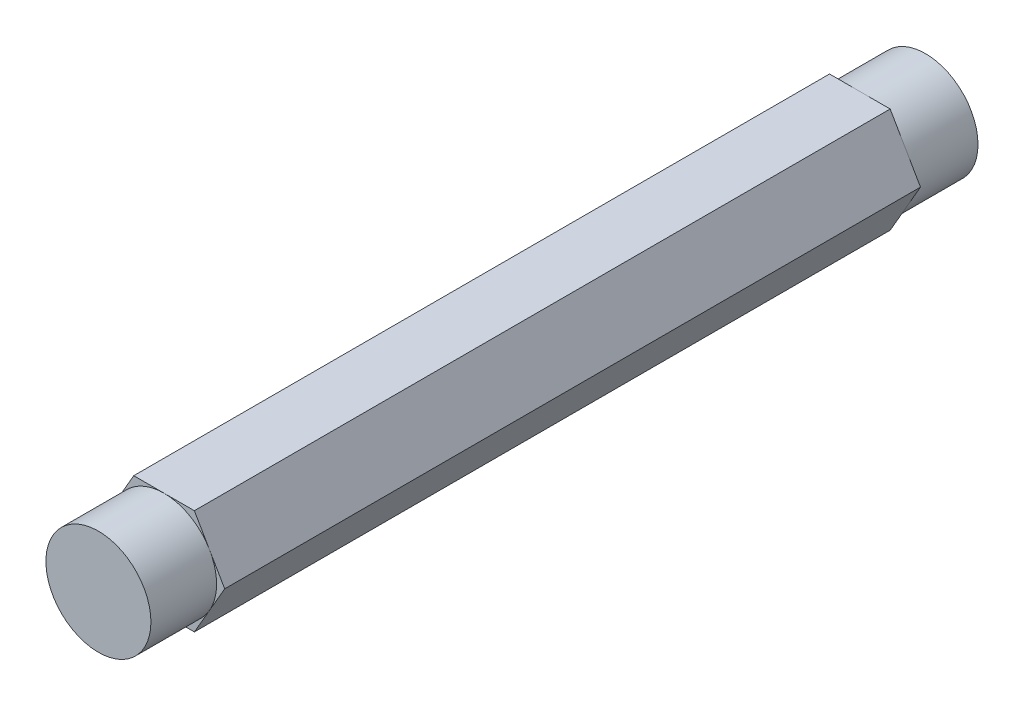
SolidWorks part; units mm, degrees
ref_plane "Front Plane" through (0, 0, 0) normal (0, 0, 1) x (1, 0, 0)
ref_plane "Top Plane" through (0, 0, 0) normal (0, 1, 0) x (1, 0, 0)
ref_plane "Right Plane" through (0, 0, 0) normal (1, 0, 0) x (0, 0, -1)
sketch "Sketch1" plane through (0, 0, 0) normal (0, 0, 1) x (1, 0, 0)
  line L1 (3.6662, 6.35) -> (-3.6662, 6.35)
  line L2 (-3.6662, 6.35) -> (-7.3323, 0)
  line L3 (-7.3323, 0) -> (-3.6662, -6.35)
  line L4 (-3.6662, -6.35) -> (3.6662, -6.35)
  line L5 (3.6662, -6.35) -> (7.3323, 0)
  line L6 (7.3323, 0) -> (3.6662, 6.35)
  circle A0 centre (0, 0) radius 6.35 construction
  point P1 (0, 6.35)
  dimension "D1" = 12.7
extrude "Boss-Extrude1" add sketch "Sketch1" along normal mid plane 100.0125
sketch "Sketch2" plane through (0, 0, 50.0062) normal (0, 0, 1) x (1, 0, 0)
  circle A0 centre (0, 0) radius 6.35
  dimension "D1" = 12.7
extrude "Cut-Extrude1" cut sketch "Sketch2" against normal blind 7.9375 flip side to cut
mirror "Mirror1" about plane through (0, 0, 0) normal (0, 0, 1) of "Cut-Extrude1"
